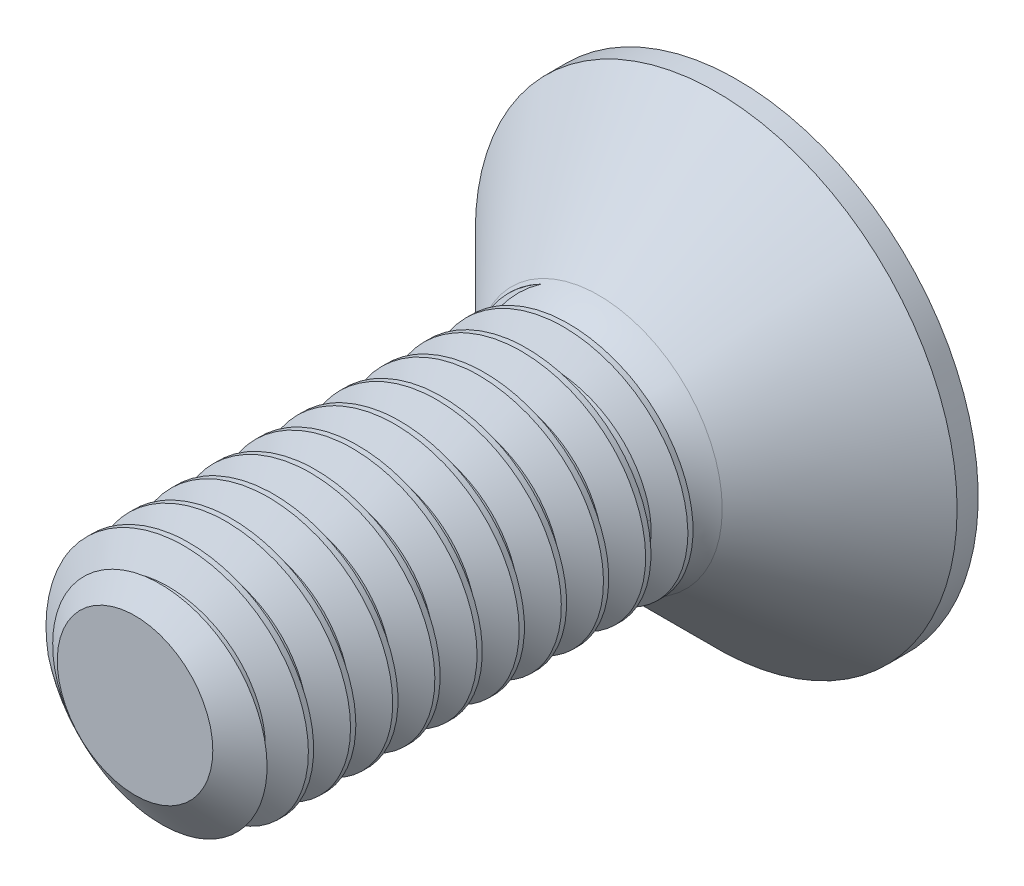
SolidWorks part; units mm, degrees
ref_plane "Front Plane" through (0, 0, 0) normal (0, 0, 1) x (1, 0, 0)
ref_plane "Top Plane" through (0, 0, 0) normal (0, 1, 0) x (1, 0, 0)
ref_plane "Right Plane" through (0, 0, 0) normal (1, 0, 0) x (0, 0, -1)
sketch "Sketch1" plane through (0, 0, 0) normal (0, 0, 1) x (1, 0, 0)
  circle A0 centre (0, 0) radius 2
  dimension "OD" = 4
extrude "Extrude1" add sketch "Sketch1" against normal blind 10
sketch "Sketch2" plane through (0, 0, 0) normal (0, 0, 1) x (1, 0, 0)
  circle A0 centre (0, 0) radius 2 construction
  circle A1 centre (0, 0) radius 2
curve "Helix/Spiral1" pitch 0.7 height 10.7 radius 2 centre (0, 0, 0) axis (0, 0, -1) start towards (0, 1, 0) parameters "pitch"=0.7
sketch "Sketch3" plane through (0, 0, 0) normal (1, 0, 0) x (0, 0, -1)
  line L0 (-0.6125, 2) -> (-0.35, 1.5453)
  line L1 (-0.35, 1.5453) -> (-0.2625, 1.5453)
  line L2 (-0.2625, 1.5453) -> (0, 2)
  line L3 (-0.6125, 2) -> (0, 2)
  line L4 (-0.3063, 2) -> (-0.3063, 1.5453) construction
  line L5 (-0.4813, 1.7727) -> (-0.1313, 1.7727) construction
  line L6 (0, 2) -> (0, -2) construction
  dimension "D1" = 0.0875
  dimension "D2" = 0.35
  dimension "D3" = 60
sweep "Cut-Sweep1" cut profiles "Sketch3" path "Helix/Spiral1"
sketch "Sketch4" plane through (0, 0, 0) normal (1, 0, 0) x (0, 0, -1)
  line L0 (0.4962, 2) -> (0, 1.2913)
  line L1 (0, 1.2913) -> (0, 2)
  line L2 (0.4962, 2) -> (0, 2)
  line L3 (-0.6125, 2) -> (0, 2) construction
  line L4 (0, 0) -> (7.0209, 0) construction
  dimension "D1" = 55
  dimension "D2" = 0.254
revolve "Cut-Revolve1" cut sketch "Sketch4" angle 360 about L4
sketch "Sketch5" plane through (0, 0, 0) normal (1, 0, 0) x (0, 0, -1)
  line L0 (10, 0.3311) -> (10, 1.814) construction
  line L1 (10, 2.05) -> (18.1906, 2.05)
  line L2 (10, 2.05) -> (10, 0)
  line L3 (10, 0) -> (18, 0)
  line L4 (18, 1.7198) -> (18, 0)
  line L5 (18.1906, 2.05) -> (18, 1.7198)
  line L6 (0, 0) -> (9.9695, 0) construction
  point P3 (18, 2.05)
  point P10 (18, 2.05)
  dimension "D1" = 0.3302
  dimension "Thread min" = 18
  dimension "D2" = 0.05
  dimension "D3" = 30
revolve "partially thread" [suppressed] add sketch "Sketch5" angle 360 about L6
sketch "Sketch6" plane through (0, 0, -10) normal (0, 0, -1) x (-1, 0, 0)
  circle A0 centre (0, 0) radius 4
  dimension "head dia" = 8
extrude "Extrude2" add sketch "Sketch6" against normal blind 2.3
sketch "Sketch10" plane through (0, 0, 0) normal (1, 0, 0) x (0, 0, -1)
  line L0 (9.65, -4) -> (7.7, -2.05)
  line L1 (7.7, -2.05) -> (7.7, -4)
  line L2 (9.65, -4) -> (7.7, -4)
  line L3 (0, 0) -> (7.7, 0) construction
  line L4 (7.7, 4) -> (7.7, -4) construction
  line L5 (9.65, 4) -> (7.7, 4) construction
  line L6 (7.7, 2.05) -> (7.7, 4) construction
  line L7 (9.65, 4) -> (7.7, 2.05) construction
  line L8 (7.7, 4) -> (7.7, -4) construction
  line L9 (7.7, 2.05) -> (7.7, -2.05) construction
  dimension "D1" = 45
  dimension "D2" = 0.05
revolve "Cut-Revolve2" cut sketch "Sketch10" angle 360 about L3
sketch "Sketch11" plane through (0, 0, 0) normal (1, 0, 0) x (0, 0, -1)
  line L0 (-0.35, 1.5453) -> (-0.2625, 1.5453) construction
  line L1 (9.65, 4) -> (7.7, 2.05) construction
  line L2 (6.4816, 1.5453) -> (6.4816, 0)
  line L3 (6.4816, 0) -> (7.7, 0)
  line L4 (7.7, 2.05) -> (7.7, 0)
  line L5 (0, 0) -> (7.7, 0) construction
  arc A0 (7.7, 2.05) -> (6.4816, 1.5453) centre (6.4816, 3.2684) cw
revolve "Revolve1" add sketch "Sketch11" angle 360 about L3
sketch "Sketch7" plane through (0, 0, -10) normal (0, 0, 1) x (1, 0, 0)
  line L1 (0, 1.4434) -> (-1.25, 0.7217)
  line L2 (-1.25, 0.7217) -> (-1.25, -0.7217)
  line L3 (-1.25, -0.7217) -> (0, -1.4434)
  line L4 (0, -1.4434) -> (1.25, -0.7217)
  line L5 (1.25, -0.7217) -> (1.25, 0.7217)
  line L6 (1.25, 0.7217) -> (0, 1.4434)
  circle A0 centre (0, 0) radius 1.25 construction
  dimension "hex dia" = 2.5
extrude "Cut-Extrude1" cut sketch "Sketch7" along normal blind 1.875
sketch "Sketch8" plane through (0, 0, -10) normal (0, 0, 1) x (1, 0, 0)
  circle A0 centre (0, 0) radius 1.4434
extrude "Cut-Extrude2" cut sketch "Sketch8" along normal through all draft 45
sketch "Sketch9" plane through (0, 0, 0) normal (1, 0, 0) x (0, 0, -1)
  line L0 (0, 2) -> (0, -2) construction
  line L1 (3.85, 2) -> (3.85, -2) construction
  line L2 (7.7, 2) -> (7.7, -2) construction
  line L3 (7.7, -2.05) -> (7.7, -4) construction
  dimension "D1" = 3.85
equation "\"D3@Helix/Spiral1\" = \"screw length@Extrude1\"+\"pitch@Helix/Spiral1\""
equation "\"D1@Sketch3\" = \"pitch@Helix/Spiral1\"*.125"
equation "\"D2@Sketch3\" = \"pitch@Helix/Spiral1\"*.5"
equation "\"D1@Cut-Extrude1\" = \"hex dia@Sketch7\"*.75"
equation "\"D1@Sketch9\" = \"pitch@Helix/Spiral1\"*5.5"
equation "\"D2@Sketch10\" = \"D2@Sketch5\""
